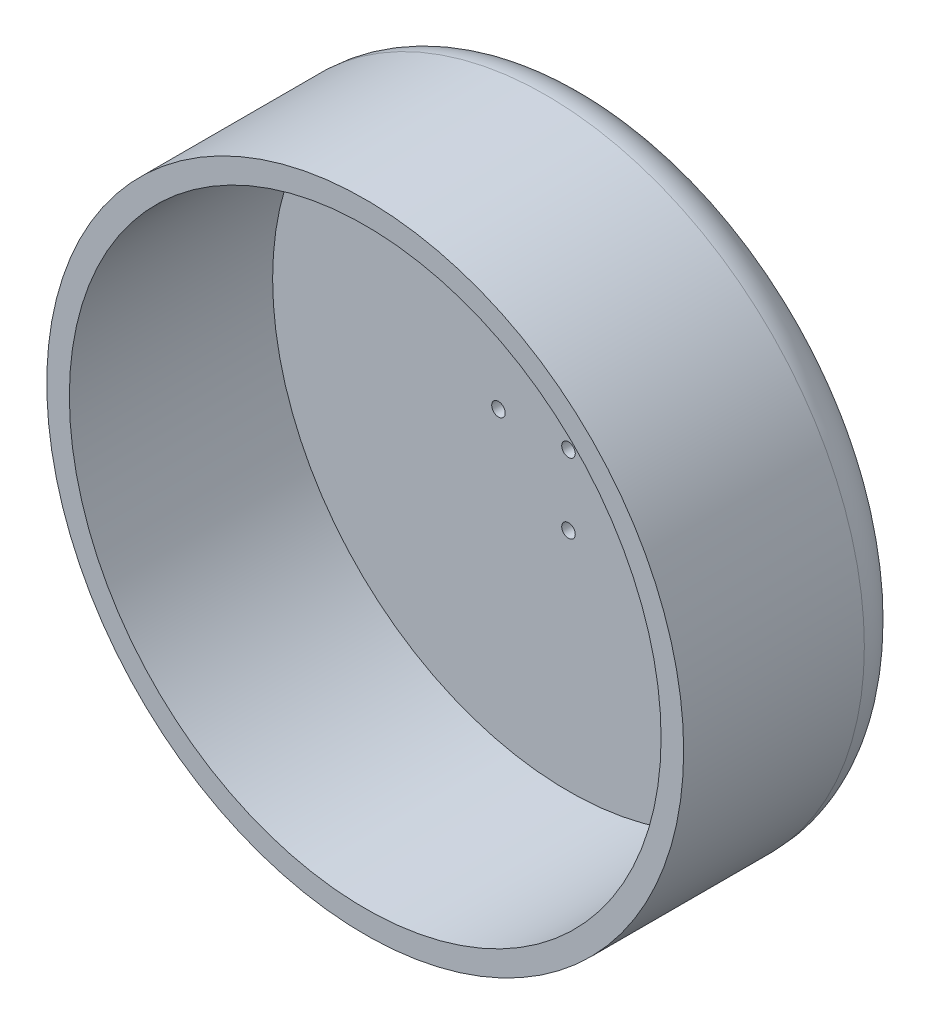
SolidWorks part; units mm, degrees
ref_plane "Alzado" through (0, 0, 0) normal (0, 0, 1) x (1, 0, 0)
ref_plane "Planta" through (0, 0, 0) normal (0, 1, 0) x (1, 0, 0)
ref_plane "Vista lateral" through (0, 0, 0) normal (1, 0, 0) x (0, 0, -1)
sketch "Croquis1" plane through (0, 0, 0) normal (0, 0, 1) x (1, 0, 0)
  circle A0 centre (0, 0) radius 65.5
  circle A1 centre (0, 0) radius 70.5
  circle A2 centre (0, 0) radius 1.5
  circle A3 centre (0, 15.5) radius 1.5
  circle A4 centre (15.5, 0) radius 1.5
  circle A5 centre (0, -15.5) radius 1.5
  circle A6 centre (-15.5, 0) radius 1.5
  dimension "D1" = 131
  dimension "D3" = 3
  dimension "D4" = 3
  dimension "D5" = 15.5
  dimension "D2" = 5
  dimension "D6" = 4
extrude "Saliente-Extruir1" add sketch "Croquis1" along normal blind 5 contours A1 A0 | A0 A6 A5 A4 A3 A2 region at (-63.6474, 0, 0) region at (-68.506, 0, 0)
extrude "Saliente-Extruir2" add sketch "Croquis1<10>" along normal blind 50 contours A1 | A0
sketch "Croquis1<10>" plane through (0, 0, 0) normal (0, 0, 1) x (1, 0, 0) same geometry as "Croquis1"
fillet "Redondeo1" radius 10 1 edges at (70.5, 0, 0)
